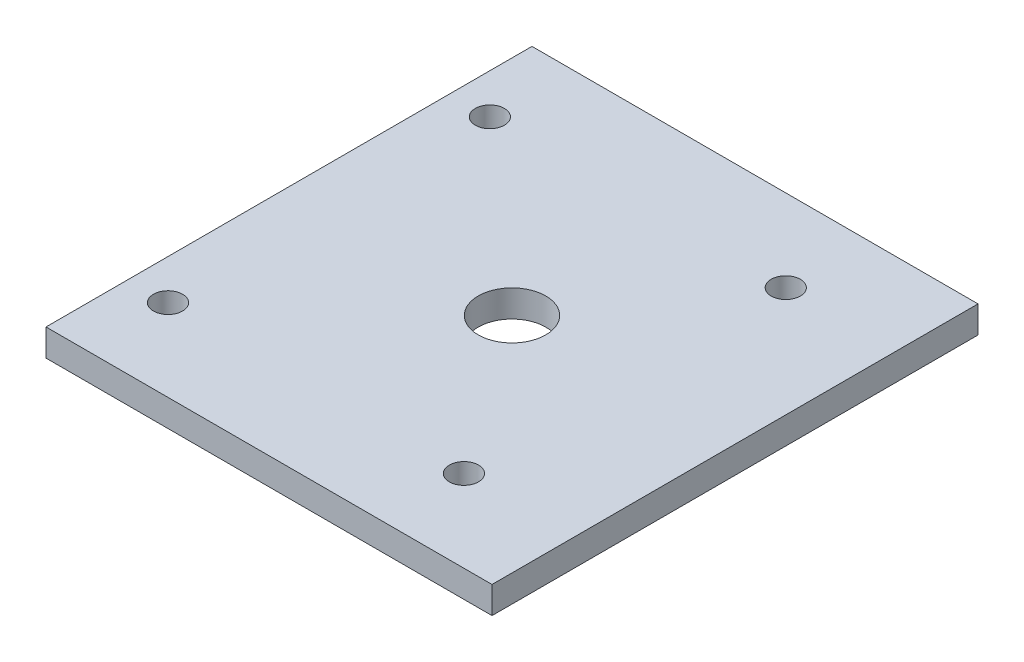
SolidWorks part; units mm, degrees
material "6061 Alloy"
ref_plane "Front Plane" through (0, 0, 0) normal (0, 0, 1) x (1, 0, 0)
ref_plane "Top Plane" through (0, 0, 0) normal (0, 1, 0) x (1, 0, 0)
ref_plane "Right Plane" through (0, 0, 0) normal (1, 0, 0) x (0, 0, -1)
sketch "Sketch1" plane through (0, 0, 0) normal (0, 1, 0) x (1, 0, 0)
  line L1 (-52.451, 57.15) -> (52.451, 57.15)
  line L2 (-52.451, 57.15) -> (-52.451, -57.15)
  line L3 (-52.451, -57.15) -> (52.451, -57.15)
  line L4 (52.451, 57.15) -> (52.451, -57.15)
  line L5 (-52.451, 57.15) -> (52.451, -57.15) construction
  line L6 (-52.451, -57.15) -> (52.451, 57.15) construction
  point P0 (0, 0)
  dimension "D1" = 114.3
  dimension "D2" = 104.902
extrude "Boss-Extrude1" add sketch "Sketch1" along normal blind 6.35
sketch "Sketch3" plane through (0, 0, 0) normal (0, -1, 0) x (1, 0, 0)
  line L0 (-8.255, 0) -> (-8.255, -20.7585) construction
  line L1 (0, 0) -> (-13.1006, 0) construction
  line L2 (-52.451, -57.15) -> (-52.451, 57.15) construction
  line L3 (-52.451, 57.15) -> (52.451, 57.15) construction
  line L4 (52.451, -57.15) -> (-52.451, -57.15) construction
  line L6 (52.451, 57.15) -> (52.451, -57.15) construction
  circle A0 centre (-43.053, 37.846) radius 3.429
  circle A1 centre (-43.053, -37.846) radius 3.429
  circle A2 centre (26.543, 37.846) radius 3.429
  circle A3 centre (26.543, -37.846) radius 3.429
  dimension "D1" = 9.398
  dimension "D4" = 25.908
  dimension "D2" = 19.304
  dimension "D3" = 19.304
extrude "Cut-Extrude2" cut sketch "Sketch3" against normal up to next
sketch "Sketch4" plane through (0, 0, 0) normal (0, -1, 0) x (1, 0, 0)
  circle A0 centre (0, 0) radius 7.9375
extrude "Cut-Extrude3" cut sketch "Sketch4" against normal up to next
